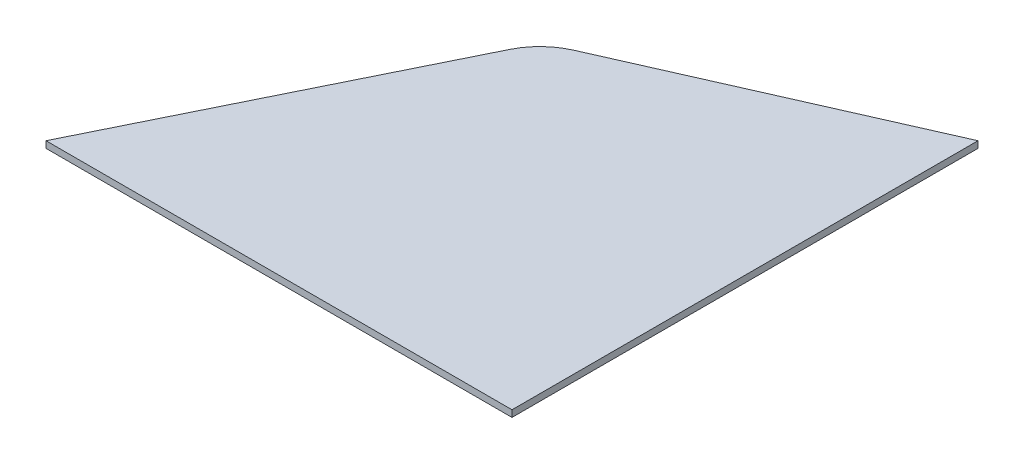
SolidWorks part; units mm, degrees
material "Hexcel AS4C (3000 Filamentos)"
ref_plane "Plano frontal" through (0, 0, 0) normal (0, 0, 1) x (1, 0, 0)
ref_plane "Plano superior" through (0, 0, 0) normal (0, 1, 0) x (1, 0, 0)
ref_plane "Plano direito" through (0, 0, 0) normal (1, 0, 0) x (0, 0, -1)
sketch "Esboço1" plane through (0, 0, 0) normal (0, 1, 0) x (1, 0, 0)
  line L0 (0, 0) -> (70, 0)
  line L1 (70, 0) -> (70, 70)
  line L2 (70, 70) -> (24.5443, 49.9521)
  line L3 (24.5443, 49.9521) -> (0, 0)
  dimension "D1" = 70
  dimension "D2" = 70
  dimension "D3" = 90
extrude "Ressalto-extrusão1" add sketch "Esboço1" along normal blind 1
fillet "Filete1" radius 10 1 edges at (24.5443, 0.5, -49.9521)
